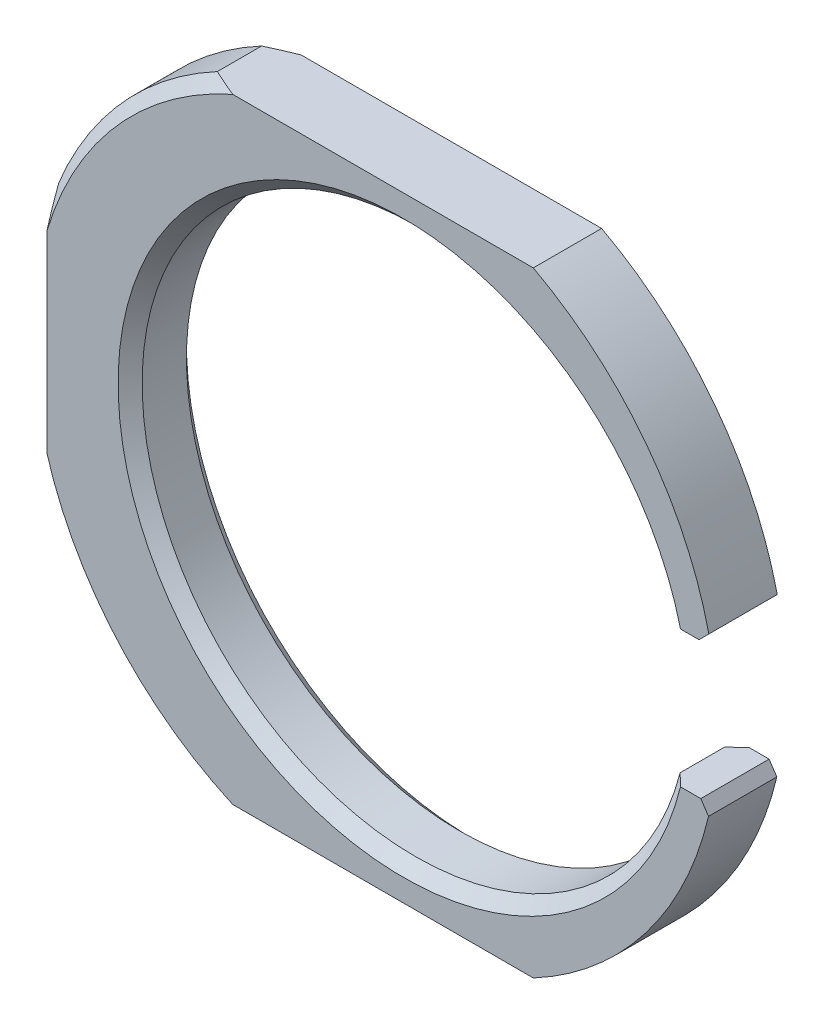
SolidWorks part; units mm, degrees
material "Plain Carbon Steel"
ref_plane "Front" through (0, 0, 0) normal (0, 0, 1) x (1, 0, 0)
ref_plane "Top" through (0, 0, 0) normal (0, 1, 0) x (1, 0, 0)
ref_plane "Right" through (0, 0, 0) normal (1, 0, 0) x (0, 0, -1)
sketch "Sketch1" plane through (0, 0, 0) normal (0, 0, 1) x (1, 0, 0)
  line L0 (13.8842, 3.175) -> (15.8782, 3.175)
  line L1 (13.8842, -3.175) -> (15.8782, -3.175)
  line L2 (7.62, 14.2875) -> (-7.62, 14.2875)
  line L3 (-7.62, -14.2875) -> (7.62, -14.2875)
  line L4 (-14.986, 6.1333) -> (-14.986, -6.1333)
  arc A0 (15.8782, 3.175) -> (7.62, 14.2875) centre (0, 0) ccw
  arc A1 (13.8842, 3.175) -> (13.8842, -3.175) centre (1.5875, 0) ccw
  arc A2 (-7.62, 14.2875) -> (-14.986, 6.1333) centre (0, 0) ccw
  arc A3 (7.62, -14.2875) -> (15.8782, -3.175) centre (0, 0) ccw
  arc A4 (-14.986, -6.1333) -> (-7.62, -14.2875) centre (0, 0) ccw
  dimension "D1" = 25.4
  dimension "D3" = 32.385
  dimension "D2" = 1.5875
  dimension "D4" = 6.35
  dimension "D5" = 3.175
  dimension "D6" = 28.575
  dimension "D7" = 14.2875
  dimension "D8" = 14.986
extrude "Boss-Extrude1" add sketch "Sketch1" along normal blind 3.175 contours A2 L4 A4 L3 A3 L1 A1 L0 A0 L2
chamfer "Chamfer1" distance 0.5588 angle 45 6 edges at (-12.0159, 10.8543, 0) (-12.0159, 10.8543, 3.175) (-11.1125, 0, 0) (-11.1125, 0, 3.175) (-12.0159, -10.8543, 0) (-12.0159, -10.8543, 3.175)
chamfer "Chamfer2" distance 0.5588 angle 45 2 edges at (15.8782, 3.175, 1.5875) (15.8782, -3.175, 1.5875) first distance on face at (14.741, 3.175, 1.6806) first distance on face at (12.3729, -9.1948, 1.5875)
equation "\"D5@Sketch1\"=\"D4@Sketch1\"/2"
equation "\"D7@Sketch1\"=\"D6@Sketch1\"/2"
